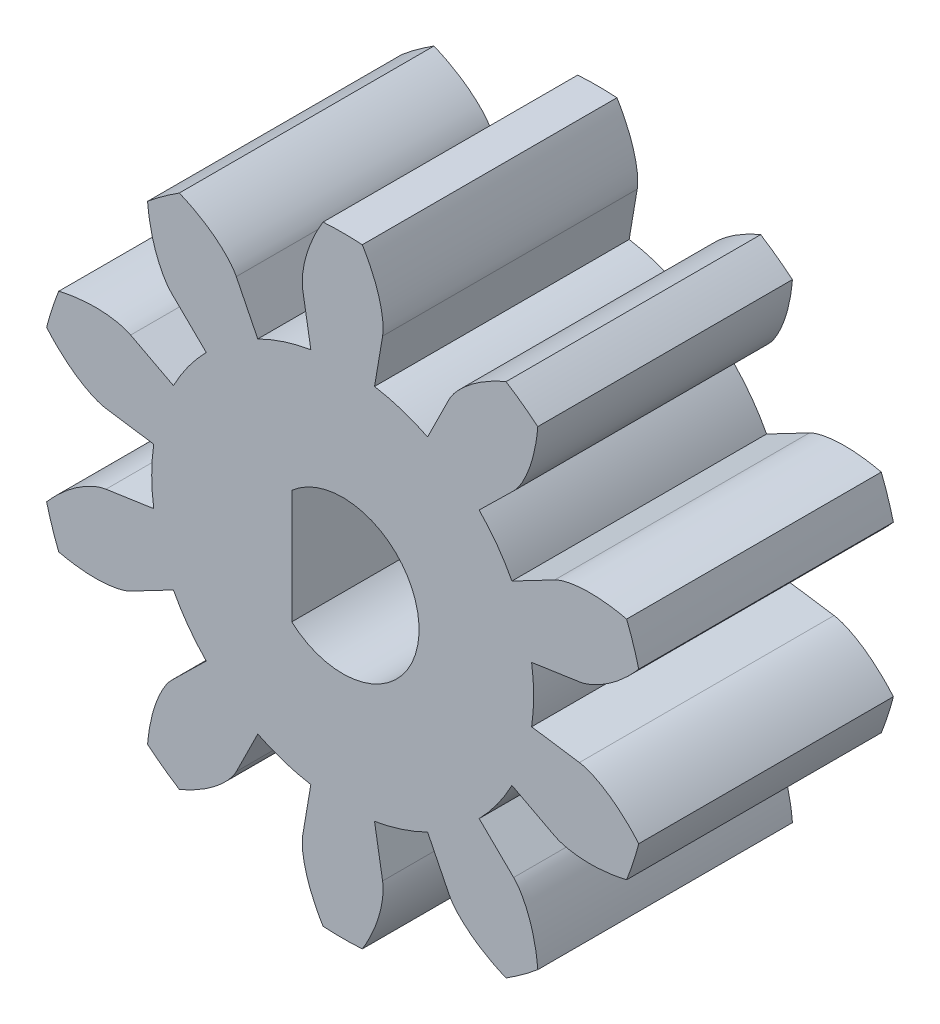
SolidWorks part; units mm, degrees
ref_plane "前视基准面" through (0, 0, 0) normal (0, 0, 1) x (1, 0, 0)
ref_plane "上视基准面" through (0, 0, 0) normal (0, 1, 0) x (1, 0, 0)
ref_plane "右视基准面" through (0, 0, 0) normal (1, 0, 0) x (0, 0, -1)
other "Configuration Table"
sketch "草图1" plane through (0, 0, 0) normal (0, 0, 1) x (1, 0, 0)
  line L0 (0, 0) -> (5, 0) construction
  line L1 (0, 0) -> (4.9384, 0.7822) construction
  line L2 (0, 0) -> (4.6481, 0.6862)
  line L3 (4.9384, 0.7822) -> (4.9384, -0.7822) construction
  line L4 (0, 0) -> (4.6481, -0.6862)
  circle A0 centre (0, 0) radius 6
  circle A1 centre (0, 0) radius 5 construction
  circle A2 centre (0, 0) radius 3.75
  circle A3 centre (0, 0) radius 4.6985 construction
  circle A4 centre (0, 0) radius 1.25
  spline S0 degree 4 poles (4.6481, 0.6862) (4.6835, 0.6914) (4.7813, 0.7134) (4.96, 0.7841) (5.2311, 0.9375) (5.5479, 1.1888) (5.9048, 1.5657) (6.2522, 2.0657) (6.551, 2.6636) (6.8384, 3.517) (6.9822, 4.4081) (6.9969, 5.3449) (6.862, 6.4517) (6.586, 7.5338) (6.0852, 8.7313) (5.3299, 9.9596) (4.4064, 11.0659) (3.3424, 12.0372) (2.1636, 12.8645) (0.8933, 13.5425) (-0.4466, 14.0687) (-1.6629, 14.396) (-2.6365, 14.5668) (-3.3507, 14.6476) (-3.7975, 14.6829) (-4.158, 14.7018) (-4.5134, 14.7121) (-4.8789, 14.7125) (-5.1964, 14.706) (-5.5003, 14.6924) (-5.8676, 14.6691) (-6.1207, 14.6466) (-6.5658, 14.6003) (-6.8589, 14.5561) (-7.1841, 14.508) (-7.4436, 14.4596) (-7.746, 14.4023) (-7.9471, 14.3573) (-8.0927, 14.3246) (-8.163, 14.308) knots 0 0 0 0 0 0.005604 0.015718 0.02996 0.048734 0.068727 0.096889 0.125051 0.153212 0.209535 0.237696 0.271429 0.327752 0.384075 0.440398 0.496721 0.553044 0.609367 0.66569 0.722013 0.778336 0.806497 0.820578 0.834659 0.84874 0.86282 0.876901 0.890982 0.900036 0.909091 0.931818 0.943182 0.954545 0.965909 0.977273 0.988636 1 1 1 1 1 construction
  spline S1 degree 4 poles (4.6481, 0.6862) (4.6835, 0.6914) (4.7813, 0.7134) (4.96, 0.7841) (5.2311, 0.9375) (5.5479, 1.1888) (5.9048, 1.5657) (6.2522, 2.0657) (6.551, 2.6636) (6.8384, 3.517) (6.9822, 4.4081) (6.9969, 5.3449) (6.862, 6.4517) (6.586, 7.5338) (6.0852, 8.7313) (5.3299, 9.9596) (4.4064, 11.0659) (3.3424, 12.0372) (2.1636, 12.8645) (0.8933, 13.5425) (-0.4466, 14.0687) (-1.6629, 14.396) (-2.6365, 14.5668) (-3.3507, 14.6476) (-3.7975, 14.6829) (-4.158, 14.7018) (-4.5134, 14.7121) (-4.8789, 14.7125) (-5.1964, 14.706) (-5.5003, 14.6924) (-5.7156, 14.6787) (-5.8219, 14.671) (-5.8742, 14.6669) knots 0 0 0 0 0 0.005604 0.015718 0.02996 0.048734 0.068727 0.096889 0.125051 0.153212 0.209535 0.237696 0.271429 0.327752 0.384075 0.440398 0.496721 0.553044 0.609367 0.66569 0.722013 0.778336 0.806497 0.820578 0.834659 0.84874 0.86282 0.876901 0.890982 0.900036 0.909091 0.909091 0.909091 0.909091 0.909091
  spline S2 degree 4 poles (4.6481, -0.6862) (4.6835, -0.6914) (4.7813, -0.7134) (4.96, -0.7841) (5.2311, -0.9375) (5.5479, -1.1888) (5.9048, -1.5657) (6.2522, -2.0657) (6.551, -2.6636) (6.8384, -3.517) (6.9822, -4.4081) (6.9969, -5.3449) (6.862, -6.4517) (6.586, -7.5338) (6.0852, -8.7313) (5.3299, -9.9596) (4.4064, -11.0659) (3.3424, -12.0372) (2.1636, -12.8645) (0.8933, -13.5425) (-0.4466, -14.0687) (-1.6629, -14.396) (-2.6365, -14.5668) (-3.3507, -14.6476) (-3.7975, -14.6829) (-4.158, -14.7018) (-4.5134, -14.7121) (-4.8789, -14.7125) (-5.1964, -14.706) (-5.5003, -14.6924) (-5.8676, -14.6691) (-6.1207, -14.6466) (-6.5658, -14.6003) (-6.8589, -14.5561) (-7.1841, -14.508) (-7.4436, -14.4596) (-7.746, -14.4023) (-7.9471, -14.3573) (-8.0927, -14.3246) (-8.163, -14.308) knots 0 0 0 0 0 0.005604 0.015718 0.02996 0.048734 0.068727 0.096889 0.125051 0.153212 0.209535 0.237696 0.271429 0.327752 0.384075 0.440398 0.496721 0.553044 0.609367 0.66569 0.722013 0.778336 0.806497 0.820578 0.834659 0.84874 0.86282 0.876901 0.890982 0.900036 0.909091 0.931818 0.943182 0.954545 0.965909 0.977273 0.988636 1 1 1 1 1 construction
  spline S3 degree 4 poles (4.6481, -0.6862) (4.6835, -0.6914) (4.7813, -0.7134) (4.96, -0.7841) (5.2311, -0.9375) (5.5479, -1.1888) (5.9048, -1.5657) (6.2522, -2.0657) (6.551, -2.6636) (6.8384, -3.517) (6.9822, -4.4081) (6.9969, -5.3449) (6.862, -6.4517) (6.586, -7.5338) (6.0852, -8.7313) (5.3299, -9.9596) (4.4064, -11.0659) (3.3424, -12.0372) (2.1636, -12.8645) (0.8933, -13.5425) (-0.4466, -14.0687) (-1.6629, -14.396) (-2.6365, -14.5668) (-3.3507, -14.6476) (-3.7975, -14.6829) (-4.158, -14.7018) (-4.5134, -14.7121) (-4.8789, -14.7125) (-5.1964, -14.706) (-5.5003, -14.6924) (-5.7156, -14.6787) (-5.8219, -14.671) (-5.8742, -14.6669) knots 0 0 0 0 0 0.005604 0.015718 0.02996 0.048734 0.068727 0.096889 0.125051 0.153212 0.209535 0.237696 0.271429 0.327752 0.384075 0.440398 0.496721 0.553044 0.609367 0.66569 0.722013 0.778336 0.806497 0.820578 0.834659 0.84874 0.86282 0.876901 0.890982 0.900036 0.909091 0.909091 0.909091 0.909091 0.909091
  point P15 (4.9384, 0)
  dimension "齿顶圆直径" = 12
  dimension "分度圆直径" = 10
  dimension "齿根圆直径" = 7.5
  dimension "基圆直径" = 9.3969
  dimension "内孔直径" = 2.5
  dimension "渐近线镜像线夹角" = 9
extrude "凸台-拉伸1" add sketch "草图1" along normal blind 5 contours A0 | A4
extrude "切除-拉伸1" cut sketch "草图1<3>" along normal through all contours A2 S3 A0 S1 region at (5.04, 0, 0)
sketch "草图1<3>" plane through (0, 0, 0) normal (0, 0, 1) x (1, 0, 0) same geometry as "草图1"
pattern_circular "阵列(圆周)1" count 10 every 36 about axis through (0, 0, 5) along (0, 0, 1) of "切除-拉伸1"
sketch "草图2" plane through (0, 0, 5) normal (0, 0, 1) x (1, 0, 0)
  circle A0 centre (0, 0) radius 1.25
  circle A1 centre (0, 0) radius 5
  circle A2 centre (0, 0) radius 1.25 construction
  dimension "D1" = 10
extrude "凸台-拉伸3" add sketch "草图2" against normal up to surface (5 mm away) contours A0 up to face at (0, 0, 0)
sketch "草图3" plane through (0, 0, 0) normal (0, 0, -1) x (-1, 0, 0)
  line L0 (1, 1.118) -> (1, -1.118)
  circle A0 centre (0, 0) radius 1.5
  dimension "D1" = 3
  dimension "D2" = 1
extrude "切除-拉伸2" cut sketch "草图3" against normal through all contours L0 A0 region at (0.148, 0, 0)
equation "\"m\"= 1'模数"
equation "\"z\" = 10'齿数"
equation "\"a\"= 20度'压力角"
equation "\"d\"= \"m\" * \"z\"'分度圆直径"
equation "\"da\"= ( \"z\" + 2 ) * \"m\"'齿顶圆直径"
equation "\"df\"= ( \"z\" - 2.5 ) * \"m\"'齿根圆直径"
equation "\"s\"= 0.5 * PI * \"m\"'分度圆齿厚"
equation "\"r\"= 0.38 * \"m\"'齿根圆角"
equation "\"B\"= 0.3 * \"d\"'齿厚"
equation "\"db\"= \"m\" * \"z\" * cos ( \"a\" )'基圆直径"
equation "\"rb\"= \"db\" / 2'基圆半径"
equation "\"齿顶圆直径@草图1\"= \"da\""
equation "\"分度圆直径@草图1\"= \"d\""
equation "\"齿根圆直径@草图1\"= \"df\""
equation "\"基圆直径@草图1\"= \"db\""
equation "\"渐近线镜像线夹角@草图1\"= 360 / 4 / \"z\""
equation "\"h\"= 5'齿轮厚度"
equation "\"ir\"= 2.5'内孔直径"
equation "\"内孔直径@草图1\"= \"ir\""
equation "\"齿轮厚@凸台-拉伸1\"= \"h\""
equation "\"齿轮夹角@阵列(圆周)1\"= 360 / \"z\""
equation "\"齿数@阵列(圆周)1\"= \"z\""
